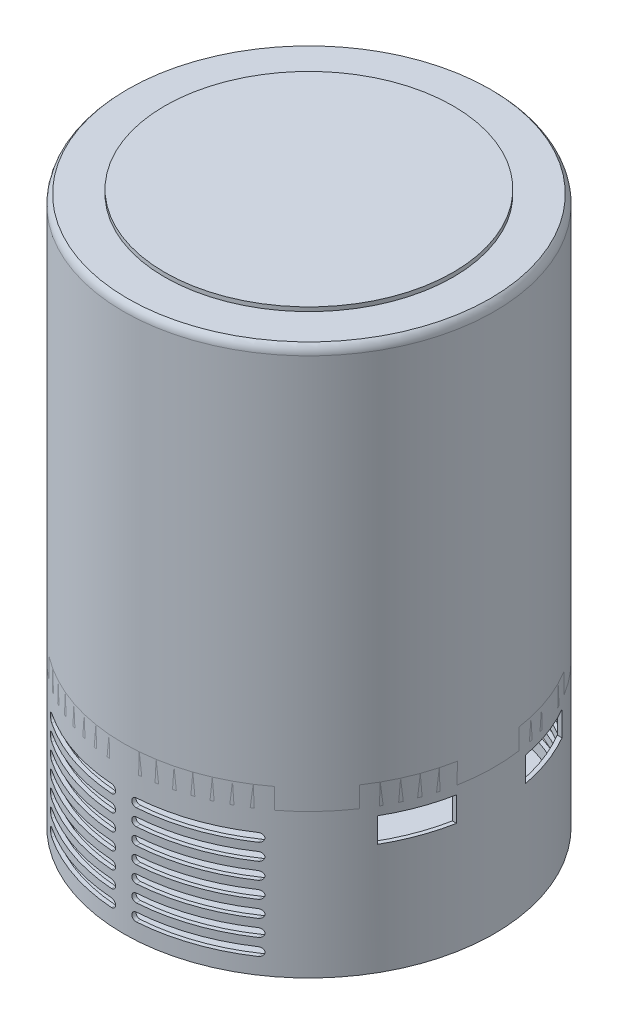
SolidWorks part; units mm, degrees
ref_plane "Front Plane" through (0, 0, 0) normal (0, 0, 1) x (1, 0, 0)
ref_plane "Top Plane" through (0, 0, 0) normal (0, 1, 0) x (1, 0, 0)
ref_plane "Right Plane" through (0, 0, 0) normal (1, 0, 0) x (0, 0, -1)
sketch "Sketch1" plane through (0, 0, 0) normal (0, 1, 0) x (1, 0, 0)
  circle A0 centre (0, 0) radius 45
  circle A1 centre (0, 0) radius 44
  dimension "D1" = 90
  dimension "D2" = 88
extrude "Boss-Extrude1" add sketch "Sketch1" along normal blind 98
fillet "Fillet1" radius 3 1 edges at (0, 98, 45)
sketch "Sketch13" plane through (0, 0, 0) normal (0, 1, 0) x (1, 0, 0)
  circle A0 centre (0, 0) radius 44
  dimension "D1" = 88
extrude "Boss-Extrude9" add sketch "Sketch13" along normal blind 2 from offset 96
sketch "Sketch5" plane through (0, 0, 0) normal (0, 1, 0) x (1, 0, 0)
  circle A0 centre (0, 0) radius 45
  dimension "D1" = 90
extrude "Boss-Extrude6" add sketch "Sketch5" against normal blind 35 separate body
sketch "Sketch6" plane through (0, 0, 0) normal (0, 1, 0) x (1, 0, 0)
  circle A0 centre (0, 0) radius 44
  dimension "D1" = 88
extrude "Cut-Extrude2" cut sketch "Sketch6" against normal blind 34
sketch "Sketch7" plane through (0, 98, 0) normal (0, 1, 0) x (1, 0, 0)
  circle A0 centre (0, 0) radius 35
  dimension "D1" = 70
extrude "Boss-Extrude7" add sketch "Sketch7" along normal blind 1
sketch "Sketch8" plane through (0, 0, 0) normal (1, 0, 0) x (0, 0, -1)
  line L0 (45, -17.5) -> (-47.6224, -17.5) construction
  line L1 (45, -35) -> (45, 0) construction
  line L3 (4, -5.5) -> (-4, -5.5)
  line L4 (4, -5.5) -> (4, -2)
  line L5 (4, -2) -> (-4, -2)
  line L6 (-4, -5.5) -> (-4, -2)
  line L7 (4, -5.5) -> (-4, -2) construction
  line L8 (4, -2) -> (-4, -5.5) construction
  line L10 (44, 0) -> (-44, 0) construction
  point P4 (0, -3.75)
  dimension "D1" = 8
  dimension "D2" = 3.5
  dimension "D3" = 2
extrude "Cut-Extrude3" cut sketch "Sketch8" against normal through all from offset 39 offset against normal yes
sketch "Sketch10" plane through (0, 0, 0) normal (0, 0, 1) x (1, 0, 0)
  line L0 (25, -6.0288) -> (3, -6.0288) construction
  line L5 (0, 12.9357) -> (0, -57.2827) construction
  line L30 (25, -5) -> (3, -5)
  line L31 (25, -7.0576) -> (3, -7.0576)
  line L32 (-25, -6.0288) -> (-3, -6.0288) construction
  line L33 (-25, -5) -> (-3, -5)
  line L34 (-25, -7.0576) -> (-3, -7.0576)
  line L35 (-25, -10.0288) -> (-3, -10.0288) construction
  line L36 (-25, -9) -> (-3, -9)
  line L37 (-25, -11.0576) -> (-3, -11.0576)
  line L38 (25, -10.0288) -> (3, -10.0288) construction
  line L39 (25, -9) -> (3, -9)
  line L40 (25, -11.0576) -> (3, -11.0576)
  line L41 (-25, -14.0288) -> (-3, -14.0288) construction
  line L42 (-25, -13) -> (-3, -13)
  line L43 (-25, -15.0576) -> (-3, -15.0576)
  line L44 (25, -14.0288) -> (3, -14.0288) construction
  line L45 (25, -13) -> (3, -13)
  line L46 (25, -15.0576) -> (3, -15.0576)
  line L47 (-25, -18.0288) -> (-3, -18.0288) construction
  line L48 (-25, -17) -> (-3, -17)
  line L49 (-25, -19.0576) -> (-3, -19.0576)
  line L50 (25, -18.0288) -> (3, -18.0288) construction
  line L51 (25, -17) -> (3, -17)
  line L52 (25, -19.0576) -> (3, -19.0576)
  line L53 (-25, -22.0288) -> (-3, -22.0288) construction
  line L54 (-25, -21) -> (-3, -21)
  line L55 (-25, -23.0576) -> (-3, -23.0576)
  line L56 (25, -22.0288) -> (3, -22.0288) construction
  line L57 (25, -21) -> (3, -21)
  line L58 (25, -23.0576) -> (3, -23.0576)
  line L59 (-25, -26.0288) -> (-3, -26.0288) construction
  line L60 (-25, -25) -> (-3, -25)
  line L61 (-25, -27.0576) -> (-3, -27.0576)
  line L62 (25, -26.0288) -> (3, -26.0288) construction
  line L63 (25, -25) -> (3, -25)
  line L64 (25, -27.0576) -> (3, -27.0576)
  line L65 (45, 0) -> (-45, 0) construction
  line L66 (-25, -30.0288) -> (-3, -30.0288) construction
  line L67 (-25, -29) -> (-3, -29)
  line L68 (-25, -31.0576) -> (-3, -31.0576)
  line L69 (-14, -8.33) -> (-14, -41.8813) construction
  line L70 (25, -30.0288) -> (3, -30.0288) construction
  line L71 (25, -29) -> (3, -29)
  line L72 (25, -31.0576) -> (3, -31.0576)
  arc A0 (-25, -5) -> (-25, -7.0576) centre (-25, -6.0288) ccw
  arc A1 (-3, -7.0576) -> (-3, -5) centre (-3, -6.0288) ccw
  arc A2 (25, -5) -> (25, -7.0576) centre (25, -6.0288) cw
  arc A3 (3, -7.0576) -> (3, -5) centre (3, -6.0288) cw
  arc A4 (-25, -9) -> (-25, -11.0576) centre (-25, -10.0288) ccw
  arc A5 (-3, -11.0576) -> (-3, -9) centre (-3, -10.0288) ccw
  arc A6 (25, -9) -> (25, -11.0576) centre (25, -10.0288) cw
  arc A7 (3, -11.0576) -> (3, -9) centre (3, -10.0288) cw
  arc A8 (-25, -13) -> (-25, -15.0576) centre (-25, -14.0288) ccw
  arc A9 (-3, -15.0576) -> (-3, -13) centre (-3, -14.0288) ccw
  arc A10 (25, -13) -> (25, -15.0576) centre (25, -14.0288) cw
  arc A11 (3, -15.0576) -> (3, -13) centre (3, -14.0288) cw
  arc A12 (-25, -17) -> (-25, -19.0576) centre (-25, -18.0288) ccw
  arc A13 (-3, -19.0576) -> (-3, -17) centre (-3, -18.0288) ccw
  arc A14 (25, -17) -> (25, -19.0576) centre (25, -18.0288) cw
  arc A15 (3, -19.0576) -> (3, -17) centre (3, -18.0288) cw
  arc A16 (-25, -21) -> (-25, -23.0576) centre (-25, -22.0288) ccw
  arc A17 (-3, -23.0576) -> (-3, -21) centre (-3, -22.0288) ccw
  arc A18 (25, -21) -> (25, -23.0576) centre (25, -22.0288) cw
  arc A19 (3, -23.0576) -> (3, -21) centre (3, -22.0288) cw
  arc A20 (-25, -25) -> (-25, -27.0576) centre (-25, -26.0288) ccw
  arc A21 (-3, -27.0576) -> (-3, -25) centre (-3, -26.0288) ccw
  arc A22 (25, -25) -> (25, -27.0576) centre (25, -26.0288) cw
  arc A23 (3, -27.0576) -> (3, -25) centre (3, -26.0288) cw
  arc A24 (-25, -29) -> (-25, -31.0576) centre (-25, -30.0288) ccw
  arc A25 (-3, -31.0576) -> (-3, -29) centre (-3, -30.0288) ccw
  arc A26 (25, -29) -> (25, -31.0576) centre (25, -30.0288) cw
  arc A27 (3, -31.0576) -> (3, -29) centre (3, -30.0288) cw
  point P3 (14, -6.0288)
  point P7 (-14, -6.0288)
  point P19 (14, -10.0288)
  point P22 (-14, -10.0288)
  point P33 (14, -14.0288)
  point P36 (-14, -14.0288)
  point P47 (14, -18.0288)
  point P50 (-14, -18.0288)
  point P61 (14, -22.0288)
  point P64 (-14, -22.0288)
  point P75 (14, -26.0288)
  point P78 (-14, -26.0288)
  point P90 (-14, -30.0288)
  point P101 (14, -30.0288)
  dimension "D1" = 22
  dimension "D2" = 6
  dimension "D3" = 5
  dimension "D5" = 1.9424
  dimension "D4" = 1.9424
extrude "Cut-Extrude5" cut sketch "Sketch10" against normal blind 10 from offset 36 offset against normal yes
sketch "Sketch12" plane through (0, 0, 0) normal (0, 0, 1) x (1, 0, 0)
  line L0 (25, -6.0288) -> (3, -6.0288) construction
  line L5 (0, 12.9357) -> (0, -57.2827) construction
  line L30 (25, -5) -> (3, -5)
  line L31 (25, -7.0576) -> (3, -7.0576)
  line L32 (-25, -6.0288) -> (-3, -6.0288) construction
  line L33 (-25, -5) -> (-3, -5)
  line L34 (-25, -7.0576) -> (-3, -7.0576)
  line L35 (-25, -10.0288) -> (-3, -10.0288) construction
  line L36 (-25, -9) -> (-3, -9)
  line L37 (-25, -11.0576) -> (-3, -11.0576)
  line L38 (25, -10.0288) -> (3, -10.0288) construction
  line L39 (25, -9) -> (3, -9)
  line L40 (25, -11.0576) -> (3, -11.0576)
  line L41 (-25, -14.0288) -> (-3, -14.0288) construction
  line L42 (-25, -13) -> (-3, -13)
  line L43 (-25, -15.0576) -> (-3, -15.0576)
  line L44 (25, -14.0288) -> (3, -14.0288) construction
  line L45 (25, -13) -> (3, -13)
  line L46 (25, -15.0576) -> (3, -15.0576)
  line L47 (-25, -18.0288) -> (-3, -18.0288) construction
  line L48 (-25, -17) -> (-3, -17)
  line L49 (-25, -19.0576) -> (-3, -19.0576)
  line L50 (25, -18.0288) -> (3, -18.0288) construction
  line L51 (25, -17) -> (3, -17)
  line L52 (25, -19.0576) -> (3, -19.0576)
  line L53 (-25, -22.0288) -> (-3, -22.0288) construction
  line L54 (-25, -21) -> (-3, -21)
  line L55 (-25, -23.0576) -> (-3, -23.0576)
  line L56 (25, -22.0288) -> (3, -22.0288) construction
  line L57 (25, -21) -> (3, -21)
  line L58 (25, -23.0576) -> (3, -23.0576)
  line L59 (-25, -26.0288) -> (-3, -26.0288) construction
  line L60 (-25, -25) -> (-3, -25)
  line L61 (-25, -27.0576) -> (-3, -27.0576)
  line L62 (25, -26.0288) -> (3, -26.0288) construction
  line L63 (25, -25) -> (3, -25)
  line L64 (25, -27.0576) -> (3, -27.0576)
  line L65 (45, 0) -> (-45, 0) construction
  line L66 (-25, -29) -> (-3, -29) construction
  line L67 (-25, -29) -> (-3, -29)
  line L68 (-25, -31.0576) -> (-3, -31.0576) construction
  line L69 (-25, -31.0576) -> (-3, -31.0576)
  line L70 (25, -31.0576) -> (3, -31.0576) construction
  line L71 (25, -29) -> (3, -29) construction
  line L72 (25, -31.0576) -> (3, -31.0576)
  line L73 (25, -29) -> (3, -29)
  arc A0 (-25, -5) -> (-25, -7.0576) centre (-25, -6.0288) ccw
  arc A1 (-3, -7.0576) -> (-3, -5) centre (-3, -6.0288) ccw
  arc A2 (25, -5) -> (25, -7.0576) centre (25, -6.0288) cw
  arc A3 (3, -7.0576) -> (3, -5) centre (3, -6.0288) cw
  arc A4 (-25, -9) -> (-25, -11.0576) centre (-25, -10.0288) ccw
  arc A5 (-3, -11.0576) -> (-3, -9) centre (-3, -10.0288) ccw
  arc A6 (25, -9) -> (25, -11.0576) centre (25, -10.0288) cw
  arc A7 (3, -11.0576) -> (3, -9) centre (3, -10.0288) cw
  arc A8 (-25, -13) -> (-25, -15.0576) centre (-25, -14.0288) ccw
  arc A9 (-3, -15.0576) -> (-3, -13) centre (-3, -14.0288) ccw
  arc A10 (25, -13) -> (25, -15.0576) centre (25, -14.0288) cw
  arc A11 (3, -15.0576) -> (3, -13) centre (3, -14.0288) cw
  arc A12 (-25, -17) -> (-25, -19.0576) centre (-25, -18.0288) ccw
  arc A13 (-3, -19.0576) -> (-3, -17) centre (-3, -18.0288) ccw
  arc A14 (25, -17) -> (25, -19.0576) centre (25, -18.0288) cw
  arc A15 (3, -19.0576) -> (3, -17) centre (3, -18.0288) cw
  arc A16 (-25, -21) -> (-25, -23.0576) centre (-25, -22.0288) ccw
  arc A17 (-3, -23.0576) -> (-3, -21) centre (-3, -22.0288) ccw
  arc A18 (25, -21) -> (25, -23.0576) centre (25, -22.0288) cw
  arc A19 (3, -23.0576) -> (3, -21) centre (3, -22.0288) cw
  arc A20 (-25, -25) -> (-25, -27.0576) centre (-25, -26.0288) ccw
  arc A21 (-3, -27.0576) -> (-3, -25) centre (-3, -26.0288) ccw
  arc A22 (25, -25) -> (25, -27.0576) centre (25, -26.0288) cw
  arc A23 (3, -27.0576) -> (3, -25) centre (3, -26.0288) cw
  arc A24 (-3, -31.0576) -> (-3, -29) centre (-3, -30.0288) ccw construction
  arc A25 (-25, -29) -> (-25, -31.0576) centre (-25, -30.0288) ccw construction
  arc A26 (-3, -31.0576) -> (-3, -29) centre (-3, -30.0288) ccw
  arc A27 (-25, -29) -> (-25, -31.0576) centre (-25, -30.0288) ccw
  arc A28 (25, -31.0576) -> (25, -29) centre (25, -30.0288) ccw construction
  arc A29 (3, -29) -> (3, -31.0576) centre (3, -30.0288) ccw construction
  arc A30 (25, -31.0576) -> (25, -29) centre (25, -30.0288) ccw
  arc A31 (3, -29) -> (3, -31.0576) centre (3, -30.0288) ccw
  point P3 (14, -6.0288)
  point P7 (-14, -6.0288)
  point P19 (14, -10.0288)
  point P22 (-14, -10.0288)
  point P33 (14, -14.0288)
  point P36 (-14, -14.0288)
  point P47 (14, -18.0288)
  point P50 (-14, -18.0288)
  point P61 (14, -22.0288)
  point P64 (-14, -22.0288)
  point P75 (14, -26.0288)
  point P78 (-14, -26.0288)
  dimension "D1" = 22
  dimension "D2" = 6
  dimension "D3" = 5
extrude "Cut-Extrude6" cut sketch "Sketch12" against normal blind 10 from offset 46
sketch "Sketch15" [suppressed] plane through (0, 0, 0) normal (0, 1, 0) x (1, 0, 0)
  line L0 (-48.3245, 0) -> (49.2947, 0) construction
  line L1 (0, 0) -> (42.2862, -15.3909)
  line L2 (0, 0) -> (42.2862, 15.3909)
  circle A0 centre (0, 0) radius 45 construction
  dimension "D1" = 20
sketch "Sketch14" plane through (0, 0, 0) normal (1, 0, 0) x (0, 0, -1)
  line L0 (-47.6224, -17.5) -> (48.7265, -17.5) construction
  line L2 (-8.3909, -8) -> (-22.3909, -8)
  line L3 (-8.3909, -8) -> (-8.3909, -2)
  line L4 (-8.3909, -2) -> (-22.3909, -2)
  line L5 (-22.3909, -8) -> (-22.3909, -2)
  line L6 (-8.3909, -8) -> (-22.3909, -2) construction
  line L7 (-8.3909, -2) -> (-22.3909, -8) construction
  line L8 (22.3909, -8) -> (8.3909, -8)
  line L9 (22.3909, -8) -> (22.3909, -2)
  line L10 (22.3909, -2) -> (8.3909, -2)
  line L11 (8.3909, -8) -> (8.3909, -2)
  line L12 (22.3909, -8) -> (8.3909, -2) construction
  line L13 (22.3909, -2) -> (8.3909, -8) construction
  line L16 (-44, 0) -> (44, 0) construction
  line L17 (0, 16.6073) -> (0, -22.4392) construction
  line L19 (-15.3909, 7.2444) -> (-15.3909, -11.5076) construction
  line L20 (15.3909, 7.2444) -> (15.3909, -11.5076) construction
  point P3 (-15.3909, -5)
  point P8 (15.3909, -5)
  point P26 (-15.3909, -2)
  dimension "D1" = 14
  dimension "D2" = 6
  dimension "D3" = 14
  dimension "D4" = 6
  dimension "D7" = 2
  dimension "D8" = 2
extrude "Cut-Extrude7" cut sketch "Sketch14" along normal blind 10 from offset 36
sketch "Sketch17" plane through (0, 0, 0) normal (0, 1, 0) x (1, 0, 0)
  circle A0 centre (0, 0) radius 45
extrude "Extrude-Thin1" add sketch "Sketch17" along normal blind 5 thin thin type one direction reverse wall 1
